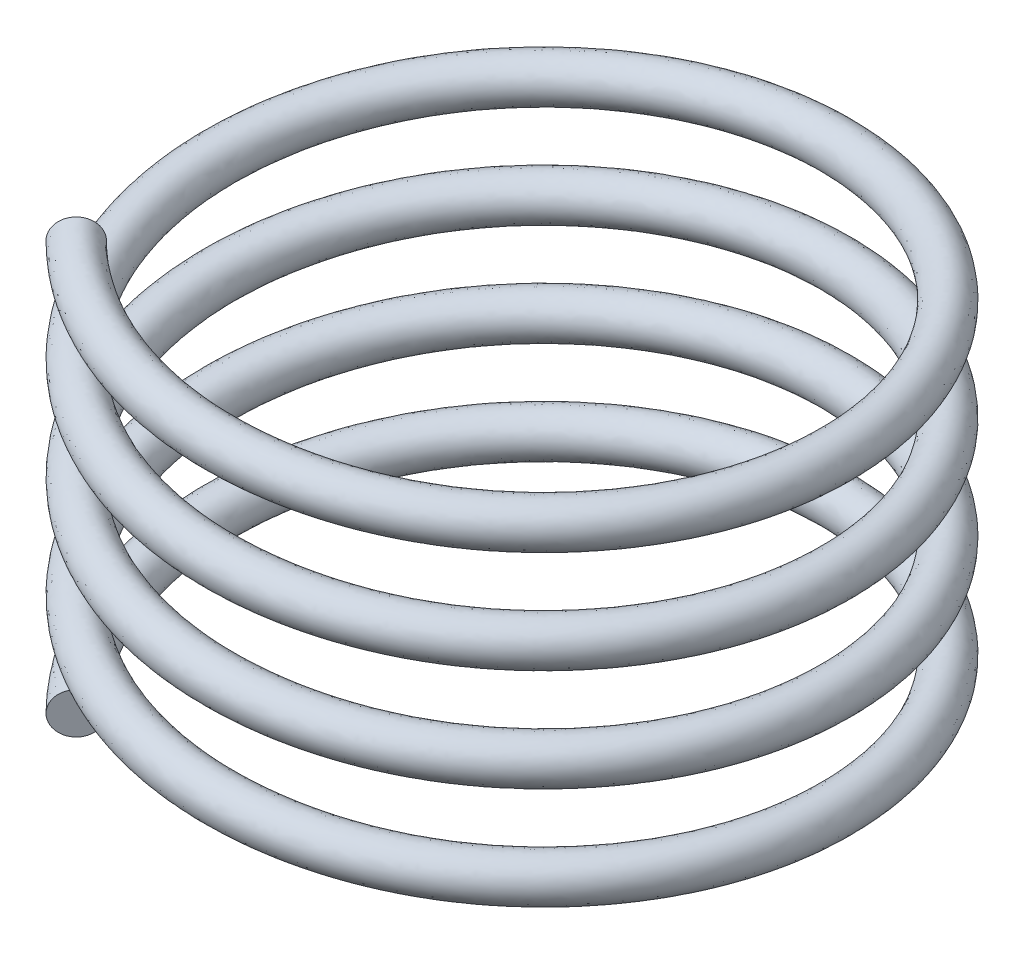
SolidWorks part; units mm, degrees
note: The reader was unsure of these and kept them because the rebuilt part matched: shared geometry of "Sketch1<2>".
ref_plane "Front Plane" through (0, 0, 0) normal (0, 0, 1) x (1, 0, 0)
ref_plane "Top Plane" through (0, 0, 0) normal (0, 1, 0) x (1, 0, 0)
ref_plane "Right Plane" through (0, 0, 0) normal (1, 0, 0) x (0, 0, -1)
sketch "Sketch1" plane through (0, 0, 0) normal (0, 1, 0) x (1, 0, 0)
  circle A0 centre (0, 0) radius 4.675
  dimension "D1" = 9.35
curve "Helix/Spiral1" pitch 1.5557 height 6.223 turns 4 parameters "length"=6.223
ref_plane "Plane2" through (-3.3057, 0, 3.3057) normal (-0.7061, 0.0529, -0.7061) x (-0.6997, 0.1009, 0.7073)
sketch "Sketch4" plane through (-3.3057, 0, 3.3057) normal (-0.7061, 0.0529, -0.7061) x (-0.6997, 0.1009, 0.7073)
  circle A0 centre (0.0093, 0.0036) radius 0.325
  dimension "D1" = 0.65
sweep "Sweep1" add profiles "Sketch4" path "Helix/Spiral1"
surface "Surface-Extrude2" sketch "Sketch1<2>"
sketch "Sketch1<2>" plane through (0, 0, 0) normal (0, 1, 0) x (1, 0, 0) same geometry as "Sketch1"
